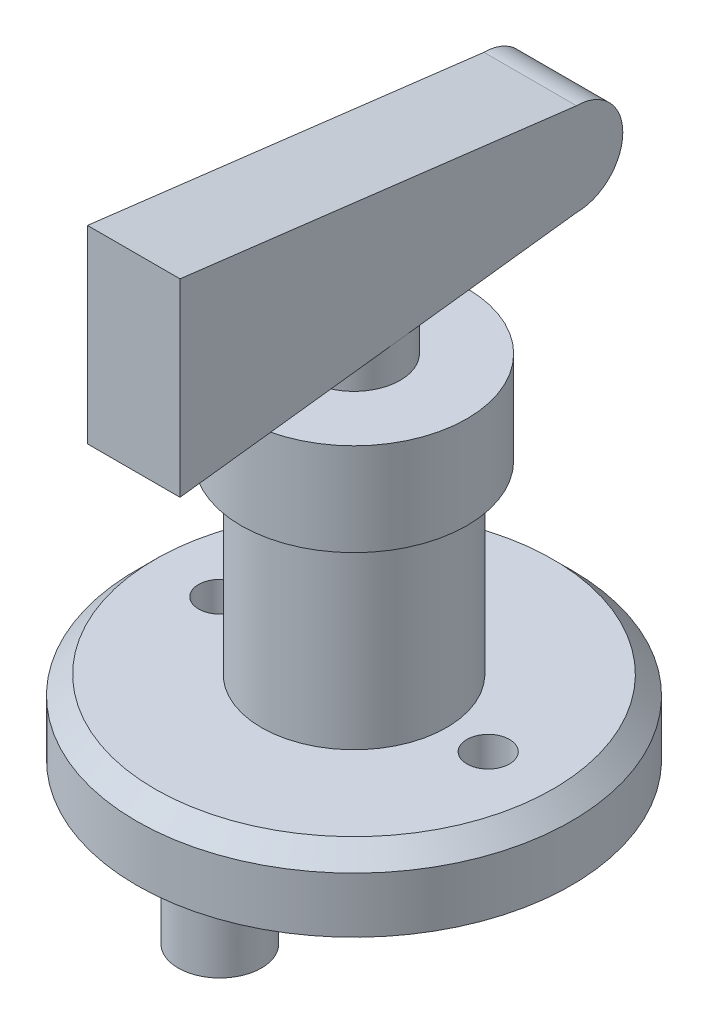
SolidWorks part; units mm, degrees
other "KeyFlag"
other "KeyBase"
ref_plane "Front Plane" through (0, 0, 0) normal (0, 0, 1) x (1, 0, 0)
ref_plane "Top Plane" through (0, 0, 0) normal (0, 1, 0) x (1, 0, 0)
ref_plane "Right Plane" through (0, 0, 0) normal (1, 0, 0) x (0, 0, -1)
sketch "Sketch1" plane through (0, 0, 0) normal (0, 1, 0) x (1, 0, 0)
  line L0 (0, 0) -> (-29.845, 0) construction
  line L1 (0, 0) -> (0, -29.845) construction
  circle A0 centre (0, 0) radius 29.845
  circle A1 centre (18.415, 0) radius 2.921
  circle A2 centre (0, 18.415) radius 5.715
  circle A3 centre (0, -18.415) radius 5.715
  circle A4 centre (-18.415, 0) radius 2.921
  point P13 (0, 12.7)
  point P14 (0, -12.7)
  dimension "D1" = 59.69
  dimension "D3" = 5.842
  dimension "D5" = 11.43
  dimension "D2" = 36.83
  dimension "D4" = 36.83
sketch "Sketch2" plane through (0, 0, 0) normal (0, 1, 0) x (1, 0, 0)
  circle A0 centre (0, 0) radius 29.845 construction
  circle A1 centre (0, 0) radius 29.845
extrude "Boss-Extrude1" add sketch "Sketch2" along normal blind 10.16
extrude "Boss-Extrude2" add sketch "Sketch1" against normal blind 12.7 contours A2 | A3
extrude "Cut-Extrude1" cut sketch "Sketch1<3>" along normal blind 12.7 contours A1 | A4
sketch "Sketch1<3>" plane through (0, 0, 0) normal (0, 1, 0) x (1, 0, 0) same geometry as "Sketch1"
sketch "Sketch3" plane through (0, 10.16, 0) normal (0, 1, 0) x (1, 0, 0)
  circle A0 centre (0, 0) radius 12.7
  dimension "D1" = 25.4
extrude "Boss-Extrude3" add sketch "Sketch3" along normal blind 25.4
chamfer "Chamfer1" distance 2.54 angle 45 1 edges at (0, 10.16, 29.845)
sketch "Sketch4" plane through (0, 35.56, 0) normal (0, 1, 0) x (1, 0, 0)
  circle A0 centre (0, 0) radius 15.494
  circle A1 centre (-18.415, 0) radius 2.921 construction
extrude "Boss-Extrude4" add sketch "Sketch4" along normal blind 12.7
sketch "Sketch5" plane through (0, 48.26, 0) normal (0, 1, 0) x (1, 0, 0)
  circle A0 centre (0, 0) radius 6.35
sketch "Sketch6" plane through (0, 0, 0) normal (1, 0, 0) x (0, 0, -1)
  line L0 (24.1863, 68.8025) -> (-30.2258, 75.4354)
  line L1 (-30.2258, 75.4354) -> (-30.2258, 49.4697)
  line L2 (-30.2258, 49.4697) -> (24.1863, 56.1025)
  arc A0 (24.1863, 56.1025) -> (24.1863, 68.8025) centre (24.1863, 62.4525) ccw
extrude "Boss-Extrude5" add sketch "Sketch6" along normal mid plane 12.7 separate body
extrude "Boss-Extrude6" add sketch "Sketch5" along normal up to surface (4.1202 mm away) separate body up to face at (0, 52.7861, 3.0198)
combine bodies "Combine1" operation type add bodies to combine 106 107
